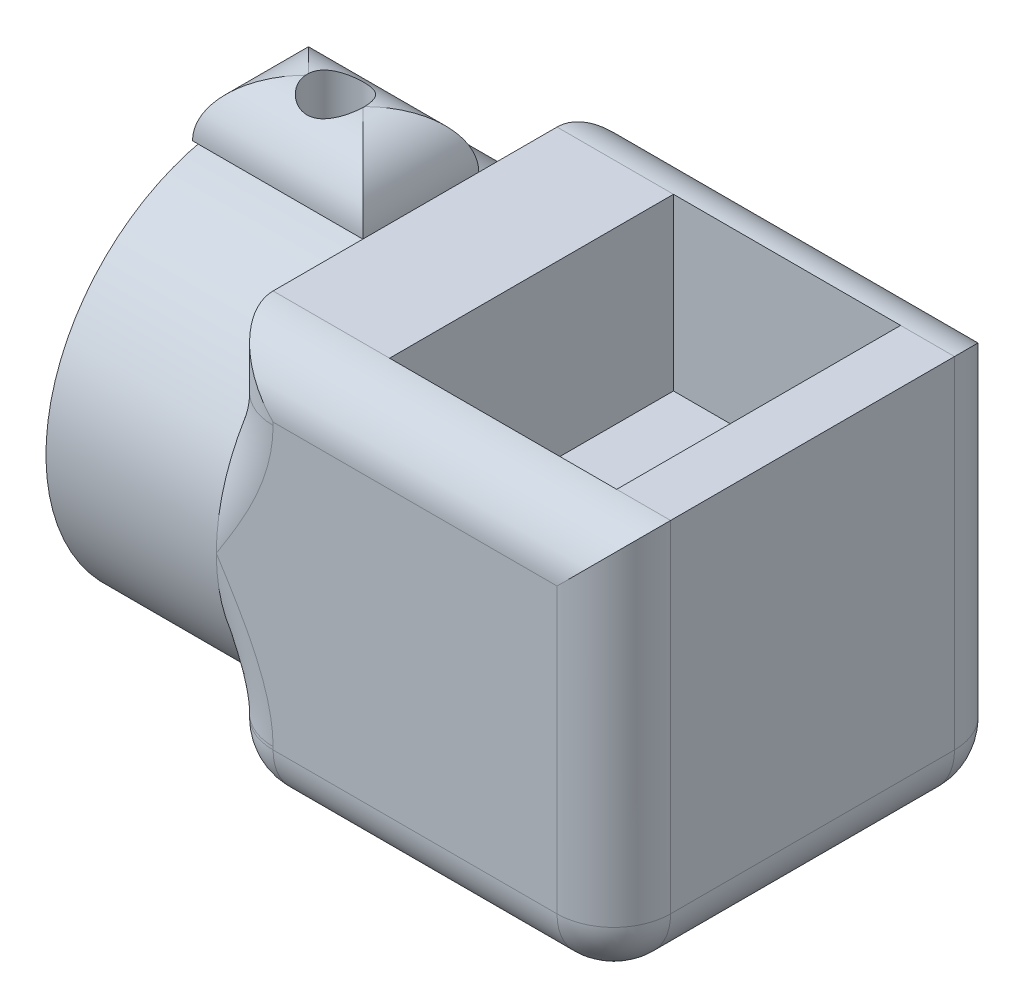
SolidWorks part; units mm, degrees
ref_plane "Front Plane" through (0, 0, 0) normal (0, 0, 1) x (1, 0, 0)
ref_plane "Top Plane" through (0, 0, 0) normal (0, 1, 0) x (1, 0, 0)
ref_plane "Right Plane" through (0, 0, 0) normal (1, 0, 0) x (0, 0, -1)
sketch "Sketch1" plane through (0, 0, 0) normal (0, 0, 1) x (1, 0, 0)
  line L1 (0, 0) -> (100, 0)
  line L2 (0, 0) -> (0, -70)
  line L3 (0, -70) -> (100, -70)
  line L4 (100, 0) -> (100, -70)
  dimension "D1" = 100
  dimension "D2" = 70
extrude "Boss-Extrude1" add sketch "Sketch1" along normal blind 70
sketch "Sketch2" plane through (0, 0, 0) normal (-1, 0, 0) x (0, 0, 1)
  circle A0 centre (35, -35) radius 30
  circle A1 centre (35, -35) radius 35
  line M1 (0, 0) -> (0, -70)
  line M2 (0, -70) -> (70, -70)
  line M3 (70, -70) -> (70, 0)
  line M4 (70, 0) -> (0, 0)
extrude "Cut-Extrude1" cut sketch "Sketch2" against normal blind 30 contours A0 | A1 M4 M1 | A1 M3 M4 | A1 M2 M3 | A1 M1 M2
fillet "Fillet1" radius 10 13 edges at (100, -35, 70) (30, -52.5, 70) (30, -17.5, 70) (65, 0, 70) (30, -70, 52.5) (65, -70, 70) (100, -70, 35) (30, -70, 17.5) (65, -70, 0) (100, -35, 0) (65, 0, 0) (30, -17.5, 0) (30, -52.5, 0)
sketch "Sketch3" plane through (0, 0, 0) normal (0, 1, 0) x (1, 0, 0)
  line L0 (100, -10) -> (30, -10) construction
  line L1 (50.508, -10) -> (90.508, -10)
  line L2 (50.508, -10) -> (50.508, -60)
  line L3 (50.508, -60) -> (90.508, -60)
  line L4 (90.508, -10) -> (90.508, -60)
  line L5 (30, -60) -> (100, -60) construction
  dimension "D1" = 40
extrude "Cut-Extrude2" cut sketch "Sketch3" against normal blind 30
sketch "Sketch4" plane through (0, 0, 0) normal (0, 1, 0) x (1, 0, 0)
  line L0 (0, 0) -> (0, -70) construction
  line L1 (0, -23.7735) -> (30, -23.7735)
  line L2 (0, -23.7735) -> (0, -44.1946)
  line L3 (0, -44.1946) -> (30, -44.1946)
  line L4 (30, -23.7735) -> (30, -44.1946)
  line L5 (30, -35) -> (30, -60) construction
extrude "Boss-Extrude2" add sketch "Sketch4" along normal blind 10 separate body
fillet "Fillet2" radius 10 4 edges at (15, 10, 23.7735) (30, 10, 33.984) (15, 10, 44.1946) (0, 10, 33.984)
sketch "Sketch5" plane through (0, 10, 0) normal (0, 1, 0) x (1, 0, 0)
  circle A0 centre (14.9432, -33.9629) radius 5
extrude "Cut-Extrude3" cut sketch "Sketch5" against normal blind 10
